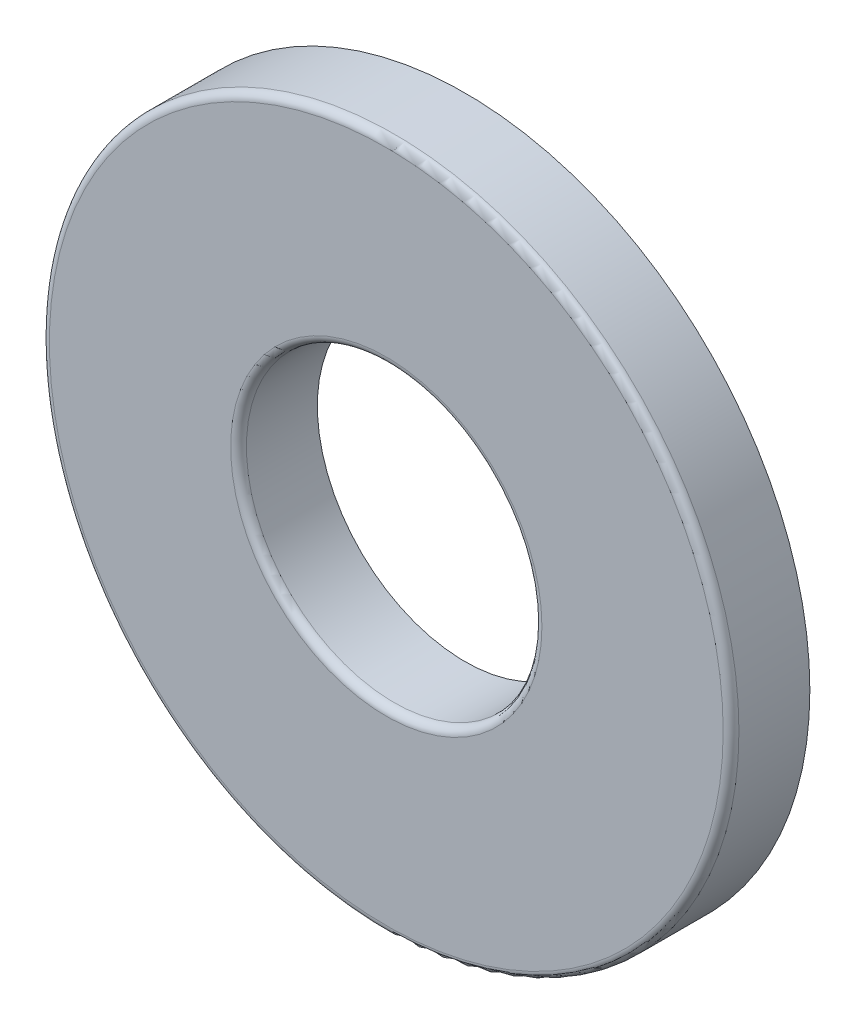
SolidWorks part; units mm, degrees
material "Alloy Steel"
ref_plane "Front Plane" through (0, 0, 0) normal (0, 0, 1) x (1, 0, 0)
ref_plane "Top Plane" through (0, 0, 0) normal (0, 1, 0) x (1, 0, 0)
ref_plane "Right Plane" through (0, 0, 0) normal (1, 0, 0) x (0, 0, -1)
sketch "Sketch1" plane through (0, 0, 0) normal (0, 0, 1) x (1, 0, 0)
  line L0 (0, 0) -> (4.7625, 0) construction
  line L1 (0, -0.943) -> (0, 0.943) construction
  circle A0 centre (0, 0) radius 11.1125
  circle A1 centre (0, 0) radius 4.7625
  dimension "D1" = 90
  dimension "OD" = 22.225
  dimension "ID" = 9.525
sketch "Sketch2" plane through (0, 0, 0) normal (1, 0, 0) x (0, 0, -1)
  line L0 (-1.27, 11.1125) -> (1.27, 11.1125) construction
  point P5 (0, 11.1125)
  dimension "Thickness" = 2.54
sketch "Sketch3" plane through (0, 0, 0) normal (0, 0, 1) x (1, 0, 0)
  circle A0 centre (0, 0) radius 4.7625 construction
  circle A1 centre (0, 0) radius 11.1125 construction
  circle A2 centre (0, 0) radius 4.7625
  circle A3 centre (0, 0) radius 11.1125
extrude "Boss-Extrude1" add sketch "Sketch3" against normal up to vertex (1.27 mm away) from vertex up to point (0, 11.1125, -1.27) starting at point (0, 11.1125, 1.27)
fillet "Fillet1" radius 0.254 2 edges at (11.1125, 0, 1.27) (4.7625, 0, 1.27)
equation "\"D1@Fillet1\"=\"Thickness@Sketch2\"/10"
